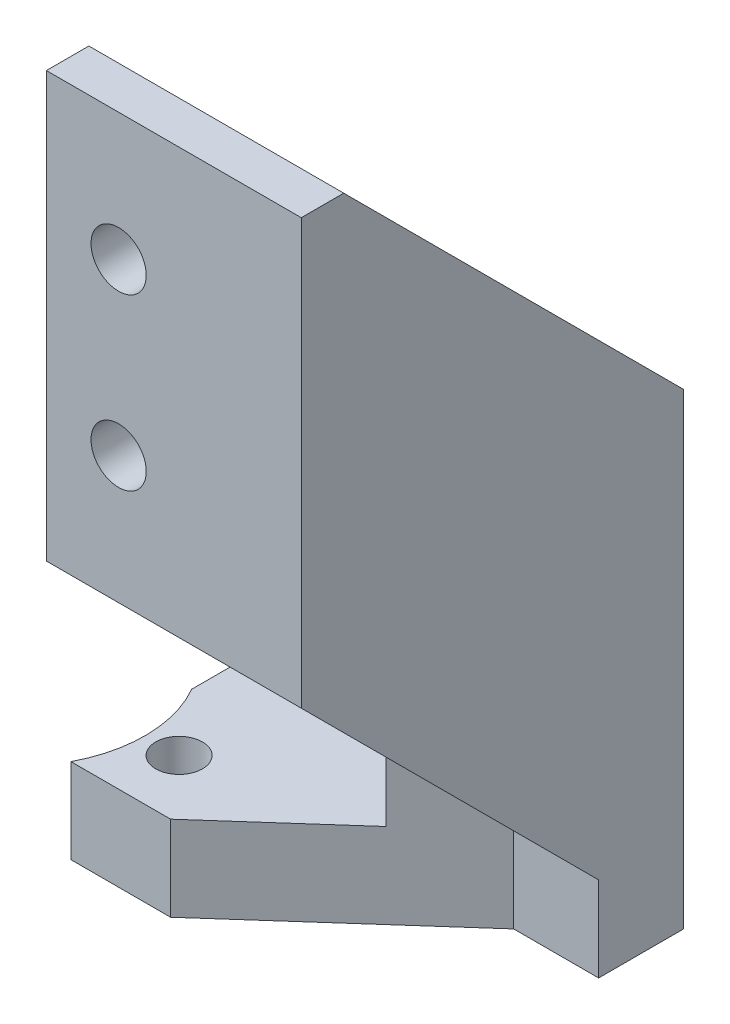
SolidWorks part; units mm, degrees
ref_plane "Plan de face" through (0, 0, 0) normal (0, 0, 1) x (1, 0, 0)
ref_plane "Plan de dessus" through (0, 0, 0) normal (0, 1, 0) x (1, 0, 0)
ref_plane "Plan de droite" through (0, 0, 0) normal (1, 0, 0) x (0, 0, -1)
sketch "Esquisse1" plane through (0, 0, 0) normal (0, 0, 1) x (1, 0, 0)
  line L1 (-40, 45) -> (0, 45)
  line L2 (-40, 45) -> (-40, 0)
  line L3 (-40, 0) -> (0, 0)
  line L4 (0, 45) -> (0, 0)
  circle A0 centre (-16.5, 32.5) radius 1.75
  circle A1 centre (-36.5, 32.5) radius 1.75
  circle A2 centre (-36.5, 12.5) radius 1.75
  circle A3 centre (-16.5, 12.5) radius 1.75
  dimension "D5" = 3.5
  dimension "D1" = 3.5
  dimension "D2" = 40
  dimension "D3" = 45
  dimension "D4" = 20
  dimension "D6" = 12.5
  dimension "D8" = 20
extrude "Boss.-Extru.1" add sketch "Esquisse1" along normal blind 10
sketch "Esquisse2" plane through (0, 0, 10) normal (0, 0, 1) x (1, 0, 0)
  circle A0 centre (-36.5, 32.5) radius 4
  circle A1 centre (-16.5, 32.5) radius 4
  circle A2 centre (-36.5, 12.5) radius 4
  circle A3 centre (-16.5, 12.5) radius 4
  dimension "D1" = 8
extrude "Enlèv. mat.-Extru.2" cut sketch "Esquisse2" against normal blind 5
sketch "Esquisse3" plane through (0, 0, 0) normal (-1, 0, 0) x (0, 0, 1)
  line L0 (10, 0) -> (45, 35)
  line L1 (45, 35) -> (45, 85)
  line L2 (45, 85) -> (40, 85)
  line L3 (40, 85) -> (0, 45)
  line L4 (10, 45) -> (0, 45) construction
  line L5 (0, 45) -> (0, 0) construction
  line L6 (0, 45) -> (10, 45)
  line L7 (10, 45) -> (10, 0)
  dimension "D1" = 45
  dimension "D2" = 30
  dimension "D3" = 50
extrude "Boss.-Extru.2" add sketch "Esquisse3" along normal blind 10
sketch "Esquisse4" plane through (-10, 0, 0) normal (-1, 0, 0) x (0, 0, 1)
  line L0 (45, 85) -> (45, 35)
  line L2 (45, 35) -> (40, 35)
  line L4 (40, 35) -> (40, 85)
  line L11 (40, 85) -> (0, 45) construction
  line L13 (40, 85) -> (45, 85)
  dimension "D1" = 5
extrude "Boss.-Extru.3" add sketch "Esquisse4" along normal blind 20
sketch "Esquisse5" plane through (0, 0, 45) normal (0, 0, 1) x (1, 0, 0)
  line L0 (-21.5, 70) -> (-21.5, 50) construction
  line L1 (-30, 85) -> (-30, 35) construction
  circle A0 centre (-21.5, 70) radius 3.25
  circle A1 centre (-21.5, 50) radius 3.25
  circle A4 centre (-36.5, 12.5) radius 1.75 construction
  circle A5 centre (-36.5, 12.5) radius 1.75 construction
  point P4 (-21.5, 60)
  point P7 (-30, 60)
  dimension "D1" = 6.5
  dimension "D2" = 20
  dimension "D3" = 15
extrude "Enlèv. mat.-Extru.3" cut sketch "Esquisse5" against normal up to next
sketch "Esquisse7" plane through (0, 0, 0) normal (0, -1, 0) x (1, 0, 0)
  line L0 (0, 0) -> (0, 10)
  line L1 (0, 10) -> (-10, 10)
  line L2 (-10, 10) -> (-31.3834, 29)
  line L3 (-31.3834, 29) -> (-43.3834, 29)
  line L4 (-43.3834, 29) -> (-43.3834, 0)
  line L5 (-43.3834, 0) -> (0, 0)
  line L6 (-40, 10) -> (-40, 0) construction
  line L7 (-40, 10) -> (-10, 10) construction
  circle A0 centre (-37.3834, 22) radius 2.75
  point P15 (0, 0)
  point P16 (-37.3834, 29)
  dimension "D2" = 5.5
  dimension "D1" = 12
  dimension "D3" = 2.6166
  dimension "D4" = 12
  dimension "D5" = 7
extrude "Boss.-Extru.4" add sketch "Esquisse7" along normal blind 10
sketch "Esquisse8" plane through (0, -10, 0) normal (0, -1, 0) x (1, 0, 0)
  circle A0 centre (-56.3834, 22) radius 15
  circle A1 centre (-37.3834, 22) radius 2.75 construction
  circle A2 centre (-37.3834, 22) radius 2.75 construction
  point P5 (0, 0)
  dimension "D2" = 30
  dimension "D1" = 19
extrude "Enlèv. mat.-Extru.5" cut sketch "Esquisse8" against normal up to next
chamfer "Chanfrein1" distance 15 angle 45 3 edges at (-10, 60, 40) (-10, 22.5, 10) (-10, 45, 5)
sketch "Esquisse6" plane through (0, 0, 40) normal (0, 0, -1) x (-1, 0, 0)
  line L0 (13.5, 70) -> (13.5, 85)
  line L1 (25, 85) -> (0, 85) construction
  line L2 (29.5, 70) -> (29.5, 85)
  line L4 (30, 85) -> (25, 85) construction
  line L5 (29.5, 85) -> (13.5, 85)
  line L6 (29.5, 50) -> (29.5, 35)
  line L8 (13.5, 50) -> (13.5, 35)
  line L9 (13.5, 35) -> (29.5, 35)
  arc A2 (29.5, 70) -> (13.5, 70) centre (21.5, 70) cw
  arc A3 (29.5, 50) -> (13.5, 50) centre (21.5, 50) ccw
  point P2 (28.6601, 35)
  point P5 (0, 0)
  point P14 (0, 0)
  point P17 (0, 0)
  point P18 (29.0119, 85)
  dimension "D1" = 8
extrude "Enlèv. mat.-Extru.4" cut sketch "Esquisse6" along normal up to next
chamfer "Chanfrein3" distance 3.5 angle 45 1 edges at (-10, 35, 35)
